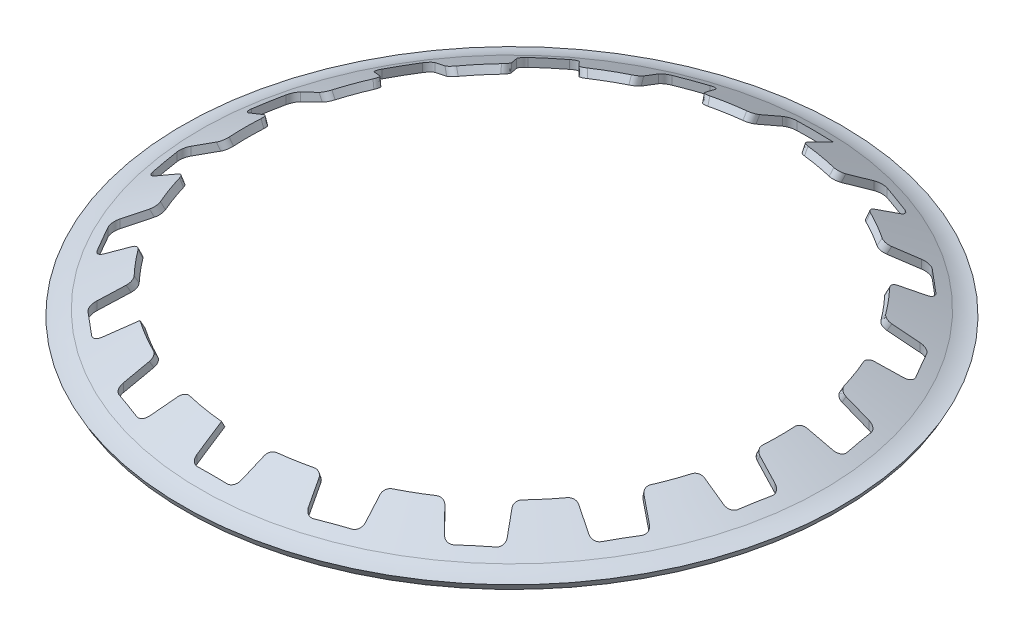
SolidWorks part; units mm, degrees
ref_plane "Plano frontal" through (0, 0, 0) normal (0, 0, 1) x (1, 0, 0)
ref_plane "Plano superior" through (0, 0, 0) normal (0, 1, 0) x (1, 0, 0)
ref_plane "Plano direito" through (0, 0, 0) normal (1, 0, 0) x (0, 0, -1)
sketch "Esboço1" plane through (0, 0, 0) normal (0, 0, 1) x (1, 0, 0)
  line L0 (0, -72.5644) -> (0, 61.8053) construction
  line L1 (44, 8.4207) -> (51.684, 4.2706)
  line L2 (54.406, 3.5206) -> (55, 4.6204)
  line L3 (52, 5.5206) -> (44.594, 9.5206)
  line L4 (44.594, 9.5206) -> (44, 8.4207)
  arc A0 (51.684, 4.2706) -> (54.406, 3.5206) centre (56.738, 17.2985) ccw
  arc A1 (55, 4.6204) -> (52, 5.5206) centre (56.135, 13.8522) cw
  dimension "D1" = 55
  dimension "D2" = 44
  dimension "D3" = 1.25
  dimension "D4" = 1.25
  dimension "D5" = 6
  dimension "D6" = 4
  dimension "D7" = 5.25
  dimension "D8" = 8
revolve "Revolução1" add sketch "Esboço1" angle 360 about L0
sketch "Esboço2" plane through (0, 0, 0) normal (0, 1, 0) x (1, 0, 0)
  line L0 (0, 44) -> (0, 0) construction
  line L1 (-3.625, 50) -> (3.625, 50)
  line L2 (-4.125, 43.4114) -> (4.125, 43.4114)
  line L3 (-4.125, 43.4114) -> (-3.625, 50)
  line L4 (4.125, 43.4114) -> (3.625, 50)
  line L6 (13.6946, 48.2245) -> (20.5074, 45.7448)
  line L7 (10.9713, 42.2042) -> (18.7238, 39.3825)
  line L8 (10.9713, 42.2042) -> (13.6946, 48.2245)
  line L9 (18.7238, 39.3825) -> (20.5074, 45.7448)
  line L11 (29.3625, 40.6323) -> (34.9163, 35.9721)
  line L12 (24.7444, 35.9065) -> (31.0642, 30.6035)
  line L13 (24.7444, 35.9065) -> (29.3625, 40.6323)
  line L14 (31.0642, 30.6035) -> (34.9163, 35.9721)
  line L16 (41.4888, 28.1393) -> (45.1138, 21.8607)
  line L17 (35.5328, 25.278) -> (39.6578, 18.1333)
  line L18 (35.5328, 25.278) -> (41.4888, 28.1393)
  line L19 (39.6578, 18.1333) -> (45.1138, 21.8607)
  line L21 (48.6109, 12.2523) -> (49.8699, 5.1125)
  line L22 (42.0356, 11.6006) -> (43.4681, 3.476)
  line L23 (42.0356, 11.6006) -> (48.6109, 12.2523)
  line L24 (43.4681, 3.476) -> (49.8699, 5.1125)
  line L26 (49.8699, -5.1125) -> (48.6109, -12.2523)
  line L27 (43.4681, -3.476) -> (42.0356, -11.6006)
  line L28 (43.4681, -3.476) -> (49.8699, -5.1125)
  line L29 (42.0356, -11.6006) -> (48.6109, -12.2523)
  line L31 (45.1138, -21.8607) -> (41.4888, -28.1393)
  line L32 (39.6578, -18.1333) -> (35.5328, -25.278)
  line L33 (39.6578, -18.1333) -> (45.1138, -21.8607)
  line L34 (35.5328, -25.278) -> (41.4888, -28.1393)
  line L36 (34.9163, -35.9721) -> (29.3625, -40.6323)
  line L37 (31.0642, -30.6035) -> (24.7444, -35.9065)
  line L38 (31.0642, -30.6035) -> (34.9163, -35.9721)
  line L39 (24.7444, -35.9065) -> (29.3625, -40.6323)
  line L41 (20.5074, -45.7448) -> (13.6946, -48.2245)
  line L42 (18.7238, -39.3825) -> (10.9713, -42.2042)
  line L43 (18.7238, -39.3825) -> (20.5074, -45.7448)
  line L44 (10.9713, -42.2042) -> (13.6946, -48.2245)
  line L46 (3.625, -50) -> (-3.625, -50)
  line L47 (4.125, -43.4114) -> (-4.125, -43.4114)
  line L48 (4.125, -43.4114) -> (3.625, -50)
  line L49 (-4.125, -43.4114) -> (-3.625, -50)
  line L51 (-13.6946, -48.2245) -> (-20.5074, -45.7448)
  line L52 (-10.9713, -42.2042) -> (-18.7238, -39.3825)
  line L53 (-10.9713, -42.2042) -> (-13.6946, -48.2245)
  line L54 (-18.7238, -39.3825) -> (-20.5074, -45.7448)
  line L56 (-29.3625, -40.6323) -> (-34.9163, -35.9721)
  line L57 (-24.7444, -35.9065) -> (-31.0642, -30.6035)
  line L58 (-24.7444, -35.9065) -> (-29.3625, -40.6323)
  line L59 (-31.0642, -30.6035) -> (-34.9163, -35.9721)
  line L61 (-41.4888, -28.1393) -> (-45.1138, -21.8607)
  line L62 (-35.5328, -25.278) -> (-39.6578, -18.1333)
  line L63 (-35.5328, -25.278) -> (-41.4888, -28.1393)
  line L64 (-39.6578, -18.1333) -> (-45.1138, -21.8607)
  line L66 (-48.6109, -12.2523) -> (-49.8699, -5.1125)
  line L67 (-42.0356, -11.6006) -> (-43.4681, -3.476)
  line L68 (-42.0356, -11.6006) -> (-48.6109, -12.2523)
  line L69 (-43.4681, -3.476) -> (-49.8699, -5.1125)
  line L71 (-49.8699, 5.1125) -> (-48.6109, 12.2523)
  line L72 (-43.4681, 3.476) -> (-42.0356, 11.6006)
  line L73 (-43.4681, 3.476) -> (-49.8699, 5.1125)
  line L74 (-42.0356, 11.6006) -> (-48.6109, 12.2523)
  line L76 (-45.1138, 21.8607) -> (-41.4888, 28.1393)
  line L77 (-39.6578, 18.1333) -> (-35.5328, 25.278)
  line L78 (-39.6578, 18.1333) -> (-45.1138, 21.8607)
  line L79 (-35.5328, 25.278) -> (-41.4888, 28.1393)
  line L81 (-34.9163, 35.9721) -> (-29.3625, 40.6323)
  line L82 (-31.0642, 30.6035) -> (-24.7444, 35.9065)
  line L83 (-31.0642, 30.6035) -> (-34.9163, 35.9721)
  line L84 (-24.7444, 35.9065) -> (-29.3625, 40.6323)
  line L86 (-20.5074, 45.7448) -> (-13.6946, 48.2245)
  line L87 (-18.7238, 39.3825) -> (-10.9713, 42.2042)
  line L88 (-18.7238, 39.3825) -> (-20.5074, 45.7448)
  line L89 (-10.9713, 42.2042) -> (-13.6946, 48.2245)
  circle A0 centre (0, 0) radius 44 construction
  point P97 (0, 0)
  dimension "D1" = 18
extrude "Corte-extrusão3" cut sketch "Esboço2" against normal through all and the other way through all contours L2 L4 L1 L3 | L87 L89 L86 L88 | L82 L84 L81 L83 | L77 L79 L76 L78 | L7 L9 L6 L8 | L12 L14 L11 L13 | L17 L19 L16 L18 | L22 L24 L21 L23 | L27 L29 L26 L28 | L32 L34 L31 L33 | L37 L39 L36 L38 | L42 L44 L41 L43 | L47 L49 L46 L48 | L52 L54 L51 L53 | L57 L59 L56 L58 | L62 L64 L61 L63 | L67 L69 L66 L68 | L72 L74 L71 L73 region at (0, 0, -46.6348) region at (15.9501, 0, -43.8224) region at (29.9763, 0, -35.7244) region at (40.387, 0, -23.3174) region at (45.9264, 0, -8.0981) region at (45.9264, 0, 8.0981) region at (40.387, 0, 23.3174) region at (29.9763, 0, 35.7244) region at (15.9501, 0, 43.8224) region at (0, 0, 46.6348) region at (-15.9501, 0, 43.8224) region at (-29.9763, 0, 35.7244) region at (-40.387, 0, 23.3174) region at (-45.9264, 0, 8.0981) region at (-40.387, 0, -23.3174) region at (-29.9763, 0, -35.7244) region at (-15.9501, 0, -43.8224)
fillet "Filete1" radius 1.25 69 edges at (-3.625, 5.8196, -50) (13.6946, 5.8196, -48.2245) (20.5074, 5.8196, -45.7448) (29.3625, 5.8196, -40.6323) (34.9163, 5.8196, -35.9721) (41.4888, 5.8196, -28.1393) (45.1138, 5.8196, -21.8607) (48.6109, 5.8196, -12.2523) (49.8699, 5.8196, -5.1125) (49.8699, 5.8196, 5.1125) (48.6109, 5.8196, 12.2523) (45.1138, 5.8196, 21.8607) (41.4888, 5.8196, 28.1393) (34.9163, 5.8196, 35.9721) (29.3625, 5.8196, 40.6323) (20.5074, 5.8196, 45.7448) (13.6946, 5.8196, 48.2245) (3.625, 5.8196, 50) (-3.625, 5.8196, 50) (-13.6946, 5.8196, 48.2245) (-20.5074, 5.8196, 45.7448) (-29.3625, 5.8196, 40.6323) (-34.9163, 5.8196, 35.9721) (-41.4888, 5.8196, 28.1393) (-45.1138, 5.8196, 21.8607) (-48.6109, 5.8196, 12.2523) (-49.8699, 5.8196, 5.1125) (-49.8699, 5.8196, -5.1125) (-48.6109, 5.8196, -12.2523) (-45.1138, 5.8196, -21.8607) (-41.4888, 5.8196, -28.1393) (-34.9163, 5.8196, -35.9721) (-29.3625, 5.8196, -40.6323) (-20.5074, 5.8196, -45.7448) (-13.6946, 5.8196, -48.2245)
